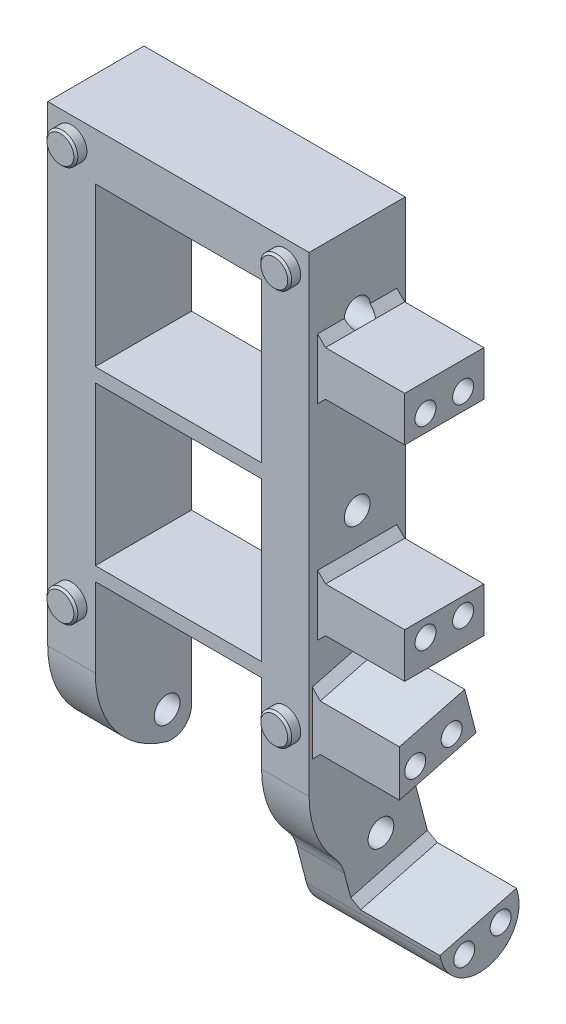
SolidWorks part; units mm, degrees
material "PBT General Purpose"
ref_plane "Front Plane" through (0, 0, 0) normal (0, 0, 1) x (1, 0, 0)
ref_plane "Top Plane" through (0, 0, 0) normal (0, 1, 0) x (1, 0, 0)
ref_plane "Right Plane" through (0, 0, 0) normal (1, 0, 0) x (0, 0, -1)
sketch "Sketch2" plane through (0, 0, 0) normal (0, 0, 1) x (1, 0, 0)
  line L0 (-33, 0) -> (33, 0)
  line L1 (33, 0) -> (33, -144)
  line L2 (33, -144) -> (21, -144)
  line L3 (21, -144) -> (21, -99)
  line L4 (21, -99) -> (-21, -99)
  line L5 (-21, -99) -> (-21, -144)
  line L6 (-21, -144) -> (-33, -144)
  line L7 (-33, -144) -> (-33, 0)
  line L8 (-21, -99) -> (-21, -95.5) construction
  line L9 (-21, -52) -> (21, -52)
  line L10 (-21, -52) -> (-21, -12)
  line L11 (-21, -12) -> (21, -12)
  line L12 (21, -52) -> (21, -12)
  line L13 (-21, -95.5) -> (21, -95.5)
  line L14 (-21, -95.5) -> (-21, -55.5)
  line L15 (-21, -55.5) -> (21, -55.5)
  line L16 (21, -95.5) -> (21, -55.5)
  line L17 (-21, -55.5) -> (-21, -52) construction
  line L18 (21, -52) -> (21, -55.5) construction
  line L19 (21, -95.5) -> (21, -99) construction
  dimension "D1" = 12
  dimension "D2" = 42
  dimension "D3" = 45
  dimension "D4" = 43.5
  dimension "D5" = 43.5
  dimension "D6" = 12
  dimension "D7" = 3.5
  dimension "D8" = 3.5
extrude "Boss-Extrude1" add sketch "Sketch2" along normal mid plane 24.3 contours L7 L0 L1 L2 L3 L4 L5 L6 | L10 L11 L12 L9 | L14 L15 L16 L13
sketch "Sketch3" plane through (0, 0, 0) normal (1, 0, 0) x (0, 0, -1)
  line L0 (-12.15, 0) -> (12.15, 0) construction
  circle A2 centre (0, -106) radius 3.25
  circle A3 centre (0, -62.5) radius 3.25
  circle A4 centre (0, -19) radius 3.25
  circle A5 centre (6, -136) radius 3.25
  dimension "D4" = 43.5
  dimension "D1" = 6.5
  dimension "D2" = 6.5
  dimension "D3" = 43.5
  dimension "D5" = 19
  dimension "D6" = 30
  dimension "D7" = 6
extrude "Cut-Extrude1" cut sketch "Sketch3" against normal through all both and the other way through all
fillet "Fillet1" radius 25 2 edges at (27, -144, 12.15) (-27, -144, 12.15)
fillet "Fillet2" radius 5 2 edges at (-27, -144, -12.15) (27, -144, -12.15)
sketch "Sketch4" plane through (0, 0, 12.15) normal (0, 0, -1) x (-1, 0, 0)
  line L5 (-33, -39.016) -> (-21, -39.016) construction
  line L6 (-27, -6) -> (27, -6) construction
  line L7 (-27, -6) -> (-27, -106) construction
  line L8 (-27, -106) -> (27, -106) construction
  line L9 (27, -6) -> (27, -106) construction
  line L10 (-33, 0) -> (-33, -138.1804) construction
  line L11 (-21, -52) -> (-21, -12) construction
  line L12 (0, -6) -> (0, 0) construction
  line L13 (33, 0) -> (-33, 0) construction
  line L14 (0, -6) -> (0, -12) construction
  line L15 (21, -12) -> (-21, -12) construction
  circle A0 centre (-27, -6) radius 3.9
  circle A1 centre (27, -6) radius 3.9
  circle A2 centre (27, -106) radius 3.9
  circle A3 centre (-27, -106) radius 3.9
  point P17 (-27, -39.016)
  dimension "D1" = 7.8
  dimension "D2" = 100
extrude "Boss-Extrude2" add sketch "Sketch4" against normal blind 2.8
chamfer "Chamfer1" distance 0.5 angle 45 4 edges at (-30.9, -106, 14.95) (23.1, -106, 14.95) (-30.9, -6, 14.95) (23.1, -6, 14.95)
ref_plane "Plane1" through (55, 0, 0) normal (1, 0, 0) x (0, 0, -1)
sketch "Sketch5" plane through (55, 0, 0) normal (1, 0, 0) x (0, 0, -1)
  line L0 (0, -62.5) -> (0, -76.89) construction
  line L1 (-4.75, -27.89) -> (4.75, -27.89) construction
  line L2 (-4.75, -27.89) -> (-4.75, -76.89) construction
  line L3 (-4.75, -76.89) -> (4.75, -76.89) construction
  line L4 (4.75, -27.89) -> (4.75, -76.89) construction
  line L5 (-7.3433, -103.7142) -> (5.0412, -151.1233) construction
  line L6 (-7.3433, -103.7142) -> (1.8483, -101.3131) construction
  line L7 (5.0412, -151.1233) -> (14.2328, -148.7223) construction
  line L8 (1.8483, -101.3131) -> (14.2328, -148.7223) construction
  line L9 (9.637, -149.9228) -> (6, -136) construction
  line L10 (12.15, 0) -> (12.15, -138.1804) construction
  circle A0 centre (6, -136) radius 3.25 construction
  dimension "D1" = 9.5
  dimension "D2" = 49
  dimension "D3" = 14.39
  dimension "D4" = 165.36
sketch "Sketch6" plane through (55, 0, 0) normal (1, 0, 0) x (0, 0, -1)
  line L0 (4.75, -52.39) -> (-4.75, -52.39) construction
  line L1 (-10, -20.89) -> (10, -20.89)
  line L2 (-10, -20.89) -> (-10, -32.19)
  line L3 (-10, -32.19) -> (10, -32.19)
  line L4 (10, -20.89) -> (10, -32.19)
  line L5 (4.75, -27.89) -> (4.75, -76.89) construction
  line L6 (-4.75, -27.89) -> (-4.75, -76.89) construction
  line L7 (-10, -72.59) -> (10, -72.59)
  line L8 (10, -83.89) -> (10, -72.59)
  line L9 (-10, -83.89) -> (10, -83.89)
  line L10 (-10, -83.89) -> (-10, -72.59)
  line L12 (0, -62.5) -> (0, -76.89) construction
  line L13 (-4.75, -27.89) -> (4.75, -27.89) construction
  line L17 (-1.1251, -148.2899) -> (18.2255, -143.235)
  line L18 (1.7309, -159.223) -> (-1.1251, -148.2899)
  line L19 (1.7309, -159.223) -> (21.0815, -154.1681)
  line L21 (21.0815, -154.1681) -> (18.2255, -143.235)
  line L25 (9.637, -149.9228) -> (6, -136) construction
  line L26 (-1.151, -127.4188) -> (8.0405, -125.0177) construction
  line L27 (-7.3433, -103.7142) -> (5.0412, -151.1233) construction
  line L28 (1.8483, -101.3131) -> (14.2328, -148.7223) construction
  line L30 (-11.336, -97.5223) -> (5.1586, -93.2135)
  line L31 (5.1586, -93.2135) -> (8.0146, -104.1466)
  line L32 (-11.336, -109.2015) -> (8.0146, -104.1466)
  line L33 (-11.336, -109.2015) -> (-11.336, -97.5223)
  line L34 (5.0412, -151.1233) -> (14.2328, -148.7223) construction
  point P16 (0, -72.59)
  point P27 (8.5502, -145.7624)
  dimension "D1" = 20
  dimension "D2" = 4.3
  dimension "D3" = 7
  dimension "D4" = 20
  dimension "D5" = 4.3
  dimension "D6" = 7
extrude "Boss-Extrude3" add sketch "Sketch6" against normal up to surface (22 mm away) up to face at (33, -136, -9.25)
sketch "Sketch8" plane through (33, 0, 0) normal (1, 0, 0) x (0, 0, -1)
  line L0 (-1.1251, -148.2899) -> (-3.9337, -137.5384)
  line L1 (12.15, 0) -> (12.15, -138.1804) construction
  line L2 (12.15, -119.9772) -> (12.15, -138.1804)
  line L3 (18.2255, -143.235) -> (12.15, -119.9772)
  line L4 (-1.1251, -148.2899) -> (1.7309, -159.223)
  line L5 (1.7309, -159.223) -> (21.0815, -154.1681)
  line L6 (21.0815, -154.1681) -> (18.2255, -143.235)
  line L7 (18.2255, -143.235) -> (-1.1251, -148.2899)
  line L8 (-1.1251, -148.2899) -> (1.7309, -159.223)
  line L9 (1.7309, -159.223) -> (21.0815, -154.1681)
  line L10 (21.0815, -154.1681) -> (18.2255, -143.235)
  arc A0 (5.725, -142.973) -> (12.15, -138.1804) centre (7.15, -138.1804) ccw construction
  arc A1 (-12.15, -119.0098) -> (5.725, -142.973) centre (12.85, -119.0098) ccw construction
  arc A2 (5.725, -142.973) -> (12.15, -138.1804) centre (7.15, -138.1804) ccw
  arc A3 (-3.9337, -137.5384) -> (5.725, -142.973) centre (12.85, -119.0098) ccw
  dimension "D1" = 0
extrude "Boss-Extrude5" add sketch "Sketch8" against normal up to surface (12 mm away) up to face at (21, -139.25, -6)
sketch "Sketch7" plane through (55, 0, 0) normal (1, 0, 0) x (0, 0, -1)
  circle A0 centre (-4.75, -27.89) radius 2.65
  circle A1 centre (4.75, -27.89) radius 2.65
  circle A2 centre (-4.75, -76.89) radius 2.65
  circle A3 centre (4.75, -76.89) radius 2.65
  circle A4 centre (-7.3433, -103.7142) radius 2.65
  circle A5 centre (1.8483, -101.3131) radius 2.65
  circle A6 centre (5.0412, -151.1233) radius 2.65
  circle A7 centre (14.2328, -148.7223) radius 2.65
  dimension "D1" = 5.3
extrude "Cut-Extrude2" cut sketch "Sketch7" against normal blind 10
fillet "Fillet3" radius 10 4 edges at (38, -159.223, -1.7309) (38, -154.1681, -21.0815) (27, -119.9772, -12.15) (27, -137.5384, 3.9337)
chamfer "Chamfer3" distance 2 angle 45 9 edges at (33, -20.89, 6.322) (33, -20.89, -6.322) (33, -32.19, 0) (33, -72.59, 0) (33, -83.89, 0) (33, -95.3679, 3.0887) (33, -104.7761, -5.6049) (33, -108.1229, 7.2069) (33, -145.7624, -8.5502)
sketch "Sketch9" plane through (33, 0, 0) normal (1, 0, 0) x (0, 0, -1)
  circle A0 centre (0, -19) radius 3.25 construction
  circle A1 centre (0, -106) radius 3.25 construction
  circle A2 centre (0, -19) radius 3.25
  circle A3 centre (0, -106) radius 3.25
extrude "Cut-Extrude3" cut sketch "Sketch9" along normal blind 2
equation "\"frisbee spacing\"= 43.5"
equation "\"D4@Sketch2\"=\"frisbee spacing\""
equation "\"D5@Sketch2\"=\"frisbee spacing\""
equation "\"D4@Sketch3\"=\"frisbee spacing\""
equation "\"D3@Sketch3\"=\"frisbee spacing\""
